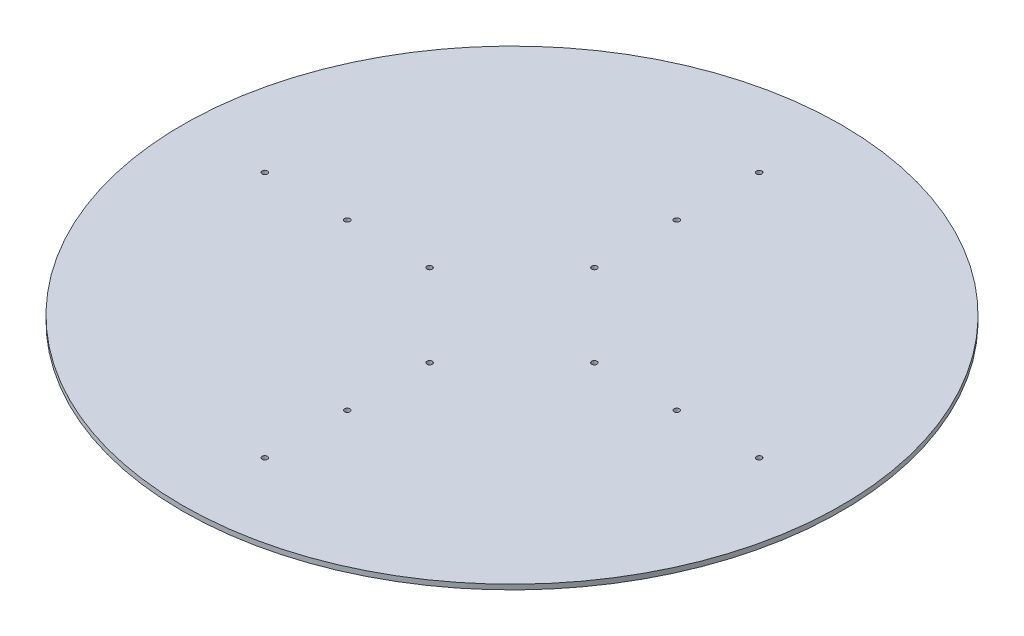
SolidWorks part; units mm, degrees
material "1060 Alloy"
ref_plane "Front Plane" through (0, 0, 0) normal (0, 0, 1) x (1, 0, 0)
ref_plane "Top Plane" through (0, 0, 0) normal (0, 1, 0) x (1, 0, 0)
ref_plane "Right Plane" through (0, 0, 0) normal (1, 0, 0) x (0, 0, -1)
sketch "Sketch3" plane through (0, 0, 0) normal (0, 1, 0) x (1, 0, 0)
  circle A0 centre (0, 0) radius 200
base flange "Base-Flange1" sketch "Sketch3" thickness 3 reverse thickness direction no parameters "D1"=3
sketch "Sketch8" plane through (0, 0, 0) normal (0, 1, 0) x (1, 0, 0)
  point P0 (0, 0)
  point P1 (0, 50)
  point P3 (0, 100)
  point P4 (0, 150)
  point P8 (50, 0)
  point P9 (100, 0)
  point P10 (150, 0)
  point P11 (0, -50)
  point P12 (0, -100)
  point P13 (0, -150)
  point P14 (-50, 0)
  point P15 (-100, 0)
  point P16 (-150, 0)
  point P17 (0, 0)
  dimension "D1" = 4
hole_wizard "#30 (0.1285) Diameter Hole1" positions "Sketch9" profile "Sketch10" hole size "#30" standard "ANSI Inch" end condition through all
sketch "Sketch9" plane through (0, 0, 0) normal (0, 1, 0) x (1, 0, 0)
  point P0 (0, 150)
  point P3 (0, 100)
  point P5 (0, 50)
  point P8 (50, 0)
  point P11 (100, 0)
  point P14 (150, 0)
  point P17 (0, -50)
  point P20 (0, -100)
  point P23 (0, -150)
  point P26 (-50, 0)
  point P29 (-100, 0)
  point P32 (-150, 0)
sketch "Sketch10" plane through (0, 0, -150) normal (1, 0, 0) x (0, 0, 1)
  line L0 (0, 0) -> (0, 3)
  line L1 (0, 3) -> (1.6319, 3)
  line L2 (1.6319, 3) -> (1.6319, 0)
  line L5 (1.6319, 0) -> (0, 0)
  line L11 (0, -6.35) -> (0, 107.95) construction
  dimension "Thru Hole Dia." = 3.2639
  dimension "Thru Hole Depth" = 3
sketch "Bend-Lines1" [suppressed] plane through (0, 0, 0) normal (0, 1, 0) x (1, 0, 0)
sketch "Bounding-Box1" [suppressed] plane through (0, 0, 0) normal (0, 1, 0) x (1, 0, 0)
sheet metal parameters "Sheet-Metal2" thickness 3 parameters "D1"=3
flat pattern "Flat-Pattern2" [suppressed]
sketch "Bend-Lines2" plane through (0, 0, 0) normal (0, 1, 0) x (1, 0, 0)
sketch3d "Bounding-Box2" [suppressed]
  line L0 (200.3122, -199.687, 0) -> (-199.687, -200.312, 0) construction
  line L1 (199.6872, 200.3122, 0) -> (-200.312, 199.6872, 0) construction
  line L2 (200.3122, -199.687, 0) -> (199.6872, 200.3122, 0) construction
  line L3 (-199.687, -200.312, 0) -> (-200.312, 199.6872, 0) construction
sheet metal parameters "Sheet-Metal3" thickness 3 parameters "D1"=3
flat pattern "Flat-Pattern2"
sketch "Bend-Lines2" plane through (0, 0, 0) normal (0, 1, 0) x (1, 0, 0)
sketch3d "Bounding-Box2" [suppressed]
  line L0 (200.3122, -199.687, 0) -> (-199.687, -200.312, 0) construction
  line L1 (199.6872, 200.3122, 0) -> (-200.312, 199.6872, 0) construction
  line L2 (200.3122, -199.687, 0) -> (199.6872, 200.3122, 0) construction
  line L3 (-199.687, -200.312, 0) -> (-200.312, 199.6872, 0) construction
